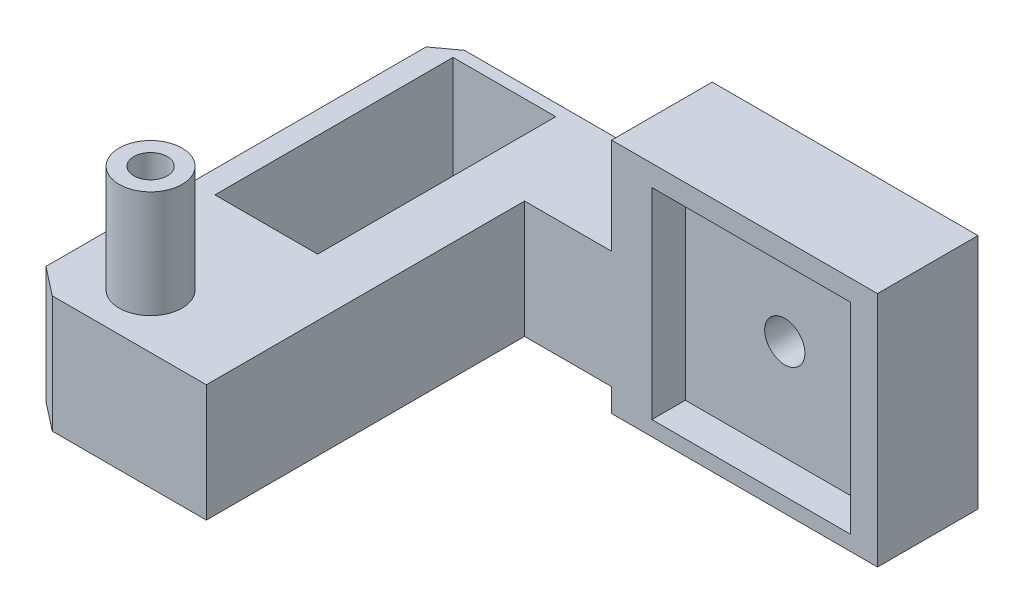
SolidWorks part; units mm, degrees
material "Custom Plastic"
ref_plane "Front Plane" through (0, 0, 0) normal (0, 0, 1) x (1, 0, 0)
ref_plane "Top Plane" through (0, 0, 0) normal (0, 1, 0) x (1, 0, 0)
ref_plane "Right Plane" through (0, 0, 0) normal (1, 0, 0) x (0, 0, -1)
sketch "Sketch1" plane through (0, 0, 0) normal (0, 0, 1) x (1, 0, 0)
  line L0 (-28.7496, 4.3597) -> (1.2504, -25.6403) construction
  line L5 (-41.2496, 16.8597) -> (13.7504, 16.8597)
  line L6 (-41.2496, 16.8597) -> (-41.2496, -38.1403)
  line L7 (-41.2496, -38.1403) -> (13.7504, -38.1403)
  line L8 (13.7504, 16.8597) -> (13.7504, -38.1403)
  line L9 (-28.7496, 4.3597) -> (1.2504, 4.3597)
  line L10 (-28.7496, 4.3597) -> (-28.7496, -25.6403)
  line L11 (-28.7496, -25.6403) -> (1.2504, -25.6403)
  line L12 (1.2504, 4.3597) -> (1.2504, -25.6403)
  line L13 (-41.2496, 16.8597) -> (13.7504, -38.1403)
  point P10 (-13.7496, -10.6403)
  point P11 (-13.7496, -10.6403)
  dimension "D1" = 55
  dimension "D2" = 30
extrude "Boss-Extrude1" add sketch "Sketch1" along normal blind 15 contours L13 L6 L7 L11 L10 | L5 L13 L9 L12 L8
sketch "Sketch5" plane through (0, 16.8597, 0) normal (0, 1, 0) x (1, 0, 0)
  line L0 (-111.2496, -70) -> (-41.2496, -70)
  line L1 (-41.2496, 0) -> (-111.2496, 0)
  line L2 (-41.2496, 0) -> (-41.2496, -70)
  line L4 (-111.2496, 0) -> (-111.2496, -70)
  dimension "D1" = 70
extrude "Boss-Extrude4" add sketch "Sketch5" against normal blind 17.5 separate body
sketch "Sketch6" plane through (0, 16.8597, 0) normal (0, 1, 0) x (1, 0, 0)
  line L0 (-111.2496, 0) -> (-111.2496, -25)
  line L1 (-111.2496, 0) -> (-111.2496, -70) construction
  line L2 (-111.2496, -25) -> (-77.2206, 0)
  line L3 (-41.2496, 0) -> (-111.2496, 0) construction
  line L4 (-77.2206, 0) -> (-111.2496, 0)
  line L5 (-111.2496, -45) -> (-76.2496, -70)
  line L6 (-111.2496, -70) -> (-41.2496, -70) construction
  line L7 (-76.2496, -70) -> (-111.2496, -70)
  line L8 (-111.2496, -70) -> (-111.2496, -45)
  line L9 (-88.2496, -8.1027) -> (-88.2496, -61.4286)
  line L10 (-88.2496, -61.4286) -> (-111.2496, -45)
  line L11 (-111.2496, -25) -> (-88.2496, -8.1027)
  line L12 (-111.2496, -45) -> (-111.2496, -25)
  line L13 (-88.2496, -61.4286) -> (-111.2496, -45)
  point P16 (-111.2496, -35)
  point P17 (-88.2496, -34.7656)
  line M9 (-111.2496, 0) -> (-111.2496, -70)
  dimension "D1" = 25
  dimension "D2" = 23
extrude "Cut-Extrude1" cut sketch "Sketch6" against normal through all contours L9 L2 L5 M9 | L8 L5 L7 | L4 L0 L2 region at (-98.0074, 16.8597, 34.8651)
sketch "Sketch8" plane through (0, 16.8597, 0) normal (0, 1, 0) x (1, 0, 0)
  line L1 (-77.1594, -1.772) -> (-61.825, -1.772)
  line L2 (-77.1594, -1.772) -> (-77.1594, -37.3148)
  line L3 (-77.1594, -37.3148) -> (-61.825, -37.3148)
  line L4 (-61.825, -1.772) -> (-61.825, -37.3148)
extrude "Cut-Extrude3" cut sketch "Sketch8" against normal through all
sketch "Sketch9" plane through (0, 16.8597, 0) normal (0, 1, 0) x (1, 0, 0)
  circle A0 centre (-69.6656, -54.4087) radius 4.7
  dimension "D1" = 9.4
extrude "Boss-Extrude5" add sketch "Sketch9" along normal blind 16
sketch "Sketch10" plane through (0, 32.8597, 0) normal (0, 1, 0) x (1, 0, 0)
  circle A0 centre (-69.6656, -54.4087) radius 2.5
  circle A1 centre (-69.6656, -54.4087) radius 4.7 construction
  dimension "D1" = 5
extrude "Cut-Extrude4" cut sketch "Sketch10" against normal blind 10
sketch "Sketch12" plane through (-732.7703, -892.3175, 5) normal (0, 0, 1) x (1, 0, 0)
  line L9 (704.0207, 896.6773) -> (734.0207, 896.6773)
  line L10 (704.0207, 896.6773) -> (704.0207, 866.6773)
  line L11 (704.0207, 866.6773) -> (734.0207, 866.6773)
  line L12 (734.0207, 896.6773) -> (734.0207, 866.6773)
extrude "Boss-Extrude6" add sketch "Sketch12" against normal blind 5
sketch "Sketch15" plane through (0, 16.8597, 0) normal (0, 1, 0) x (1, 0, 0)
  line L1 (-41.2496, 0) -> (13.7504, 0)
  line L2 (-41.2496, 0) -> (-41.2496, -15)
  line L3 (-41.2496, -15) -> (13.7504, -15)
  line L4 (13.7504, 0) -> (13.7504, -15)
extrude "Boss-Extrude7" add sketch "Sketch15" along normal blind 18.75
sketch "Sketch16" plane through (0, 0, 15) normal (0, 0, 1) x (1, 0, 0)
  line L1 (-28.7496, 4.3597) -> (1.2504, 4.3597)
  line L2 (-28.7496, 4.3597) -> (-28.7496, -25.6403)
  line L3 (-28.7496, -25.6403) -> (1.2504, -25.6403)
  line L4 (1.2504, 4.3597) -> (1.2504, -25.6403)
  line M1 (-28.7496, -25.6403) -> (-28.7496, 4.3597)
  line M2 (-28.7496, 4.3597) -> (1.2504, 4.3597)
  line M3 (1.2504, 4.3597) -> (1.2504, -25.6403)
  line M4 (1.2504, -25.6403) -> (-28.7496, -25.6403)
extrude "Boss-Extrude8" add sketch "Sketch16" against normal up to surface (10 mm away) contours M1 M4 M3 M2 region at (-13.7496, -10.6403, 15) up to face at (-13.7496, -10.6403, 5)
sketch "Sketch18" plane through (0, 0, 0) normal (0, 0, -1) x (-1, 0, 0)
  line L0 (-13.7504, 35.6097) -> (-13.7504, -38.1403) construction
  line L1 (41.2496, -38.1403) -> (-13.7504, -38.1403)
  line L2 (41.2496, -38.1403) -> (41.2496, -19.3903)
  line L3 (41.2496, -19.3903) -> (-13.7504, -19.3903)
  line L4 (-13.7504, -38.1403) -> (-13.7504, -19.3903)
  line L5 (41.2496, -0.6403) -> (41.2496, -19.3903) construction
  line L6 (41.2496, 35.6097) -> (41.2496, 16.8597) construction
extrude "Cut-Extrude6" cut sketch "Sketch18" against normal through all
sketch "Sketch19" plane through (0, 16.8597, 0) normal (0, 1, 0) x (1, 0, 0)
  line L0 (-41.2496, 0) -> (-77.2206, 0) construction
  line L1 (-41.2496, -70) -> (-53.2496, -70)
  line L2 (-41.2496, -70) -> (-41.2496, 0)
  line L3 (-41.2496, 0) -> (-53.2496, 0)
  line L4 (-53.2496, -70) -> (-53.2496, 0)
  dimension "D1" = 12
sketch "Sketch20" plane through (-41.2496, 0, 0) normal (-1, 0, 0) x (0, 0, 1)
  line L1 (0, 35.6097) -> (15, 35.6097)
  line L2 (0, 35.6097) -> (0, 16.8597)
  line L3 (0, 16.8597) -> (15, 16.8597)
  line L4 (15, 35.6097) -> (15, 16.8597)
  line L5 (15, -19.3903) -> (0, -19.3903)
  line L6 (15, -19.3903) -> (15, -0.6403)
  line L7 (15, -0.6403) -> (0, -0.6403)
  line L8 (0, -19.3903) -> (0, -0.6403)
extrude "Boss-Extrude9" add sketch "Sketch20" along normal blind 12
sketch "Sketch21" plane through (0, 16.8597, 0) normal (0, 1, 0) x (1, 0, 0)
  line L1 (-53.2496, -15) -> (-41.2496, -15)
  line L2 (-53.2496, -15) -> (-53.2496, -70)
  line L3 (-53.2496, -70) -> (-41.2496, -70)
  line L4 (-41.2496, -15) -> (-41.2496, -70)
extrude "Cut-Extrude9" cut sketch "Sketch21" against normal through all
sketch "Sketch22" plane through (0, 0, 15) normal (0, 0, 1) x (1, 0, 0)
  line L0 (-23.2496, 35.6097) -> (-23.2496, -19.3903) construction
  line L1 (-34.2496, 28.1097) -> (-4.2496, 28.1097)
  line L2 (-34.2496, 28.1097) -> (-34.2496, -1.8903)
  line L3 (-34.2496, -1.8903) -> (-4.2496, -1.8903)
  line L4 (-4.2496, 28.1097) -> (-4.2496, -1.8903)
  line L5 (-53.2496, 35.6097) -> (13.7504, 35.6097) construction
  line L6 (13.7504, -19.3903) -> (-53.2496, -19.3903) construction
  line L8 (-53.2496, 16.8597) -> (-53.2496, 35.6097) construction
  dimension "D1" = 30
  dimension "D2" = 19
  dimension "D3" = 7.5
sketch "Sketch23" plane through (0, 0, 15) normal (0, 0, 1) x (1, 0, 0)
  line L0 (-53.2496, 35.6097) -> (13.7504, 35.6097) construction
  line L1 (13.7504, 35.6097) -> (-4.572, 35.6097)
  line L2 (13.7504, 35.6097) -> (13.7504, -19.3903)
  line L3 (13.7504, -19.3903) -> (-4.572, -19.3903)
  line L4 (-4.572, 35.6097) -> (-4.572, -19.3903)
  line L5 (13.7504, -19.3903) -> (-53.2496, -19.3903) construction
  line L6 (-53.2496, -19.3903) -> (-53.2496, -0.6403) construction
  line L7 (-53.2496, -10.0153) -> (-4.572, -10.0153)
  line L8 (-53.2496, -10.0153) -> (-53.2496, -19.3903)
  line L9 (-53.2496, -19.3903) -> (-4.572, -19.3903)
  line L10 (-4.572, -10.0153) -> (-4.572, -19.3903)
  line L12 (-4.572, 26.2347) -> (-53.2496, 26.2347)
  line L13 (-4.572, 26.2347) -> (-4.572, 35.6097)
  line L14 (-4.572, 35.6097) -> (-53.2496, 35.6097)
  line L15 (-53.2496, 26.2347) -> (-53.2496, 35.6097)
  line M10 (-53.2496, -0.6403) -> (-53.2496, -19.3903)
  line M11 (-53.2496, -19.3903) -> (13.7504, -19.3903)
  line M12 (13.7504, -19.3903) -> (13.7504, 35.6097)
  line M13 (13.7504, 35.6097) -> (-53.2496, 35.6097)
  line M14 (-53.2496, 35.6097) -> (-53.2496, 16.8597)
extrude "Cut-Extrude11" cut sketch "Sketch23" against normal through all contours L7 L4 M10 M11 | L12 L4 M13 M14 | L4 M13 M11 M12 region at (4.5892, 8.1097, 15) region at (-28.9108, 30.9222, 15) region at (-28.9108, -14.7028, 15)
sketch "Sketch25" plane through (0, 16.8597, 0) normal (0, 1, 0) x (1, 0, 0)
  line L0 (-76.2496, -70) -> (-53.2496, -70) construction
  line L1 (-88.2496, -0.6439) -> (-80.5211, -0.6439)
  line L2 (-88.2496, -0.6439) -> (-88.2496, -70)
  line L3 (-88.2496, -70) -> (-80.5211, -70)
  line L4 (-80.5211, -0.6439) -> (-80.5211, -70)
  line M8 (-77.2206, 0) -> (-88.2496, -8.1027)
  line M9 (-88.2496, -8.1027) -> (-88.2496, -61.4286)
  line M10 (-88.2496, -61.4286) -> (-76.2496, -70)
extrude "Cut-Extrude13" cut sketch "Sketch25" against normal through all contours L4 M8 M9 M10 region at (-84.263, 16.8597, 34.725)
sketch "Sketch26" plane through (-53.2496, 0, 0) normal (-1, 0, 0) x (0, 0, 1)
  line L1 (0, 26.2347) -> (15, 26.2347)
  line L2 (0, 26.2347) -> (0, 16.8597)
  line L3 (0, 16.8597) -> (15, 16.8597)
  line L4 (15, 26.2347) -> (15, 16.8597)
extrude "Cut-Extrude14" cut sketch "Sketch26" against normal blind 13
sketch "Sketch27" plane through (0, 16.8597, 0) normal (0, 1, 0) x (1, 0, 0)
  line L0 (-53.2496, -70) -> (-53.2496, -62.5)
  line L1 (-53.2496, -70) -> (-53.2496, 0) construction
  line L2 (-53.2496, -62.5) -> (-76.2496, -62.5)
  line L3 (-76.2496, -62.5) -> (-80.5211, -59.1627)
  line L4 (-80.5211, -2.4248) -> (-80.5211, -66.9489) construction
  line L5 (-80.5211, -59.1627) -> (-80.5211, -66.9489)
  line L6 (-80.5211, -66.9489) -> (-76.2496, -70)
  line L7 (-76.2496, -70) -> (-53.2496, -70)
  line L8 (-76.2496, -70) -> (-76.2496, -62.5) construction
  dimension "D1" = 52
  dimension "D2" = 7.5
extrude "Cut-Extrude15" cut sketch "Sketch27" against normal through all
sketch "Sketch28" plane through (0, 26.2347, 0) normal (0, 1, 0) x (1, 0, 0)
  line L1 (-40.2496, 0) -> (-4.572, 0)
  line L2 (-40.2496, 0) -> (-40.2496, -15)
  line L3 (-40.2496, -15) -> (-4.572, -15)
  line L4 (-4.572, 0) -> (-4.572, -15)
extrude "Boss-Extrude10" add sketch "Sketch28" along normal blind 5
extrude "Cut-Extrude16" cut sketch "Sketch22" against normal blind 5
sketch "Sketch30" plane through (0, 0, 15) normal (0, 0, 1) x (1, 0, 0)
  line L0 (-53.2496, -10.0153) -> (-4.572, -10.0153) construction
  line L1 (-53.2496, -0.6403) -> (-40.2496, -0.6403)
  line L2 (-53.2496, -0.6403) -> (-53.2496, -10.0153)
  line L3 (-53.2496, -10.0153) -> (-40.2496, -10.0153)
  line L4 (-40.2496, -0.6403) -> (-40.2496, -10.0153)
  line L6 (-40.2496, -4.1188) -> (-4.572, -4.1188)
  line L7 (-40.2496, -4.1188) -> (-40.2496, -10.0153)
  line L8 (-40.2496, -10.0153) -> (-4.572, -10.0153)
  line L9 (-4.572, -4.1188) -> (-4.572, -10.0153)
extrude "Cut-Extrude18" cut sketch "Sketch30" against normal through all contours L2 L1 L4 L3 | L7 L6 L9 L8
sketch "Sketch32" plane through (-4.572, 0, 0) normal (1, 0, 0) x (0, 0, -1)
  line L1 (-15, 31.2347) -> (0, 31.2347)
  line L2 (-15, 31.2347) -> (-15, -4.1188)
  line L3 (-15, -4.1188) -> (0, -4.1188)
  line L4 (0, 31.2347) -> (0, -4.1188)
extrude "Boss-Extrude12" add sketch "Sketch32" along normal blind 4
sketch "Sketch33" plane through (0, 0, 10) normal (0, 0, 1) x (1, 0, 0)
  line L0 (-34.2496, 28.1097) -> (-4.572, -1.8903) construction
  circle A0 centre (-19.4108, 13.1097) radius 3
  point P7 (-19.4108, 13.1097)
  dimension "D1" = 6
extrude "Cut-Extrude19" cut sketch "Sketch33" against normal through all
